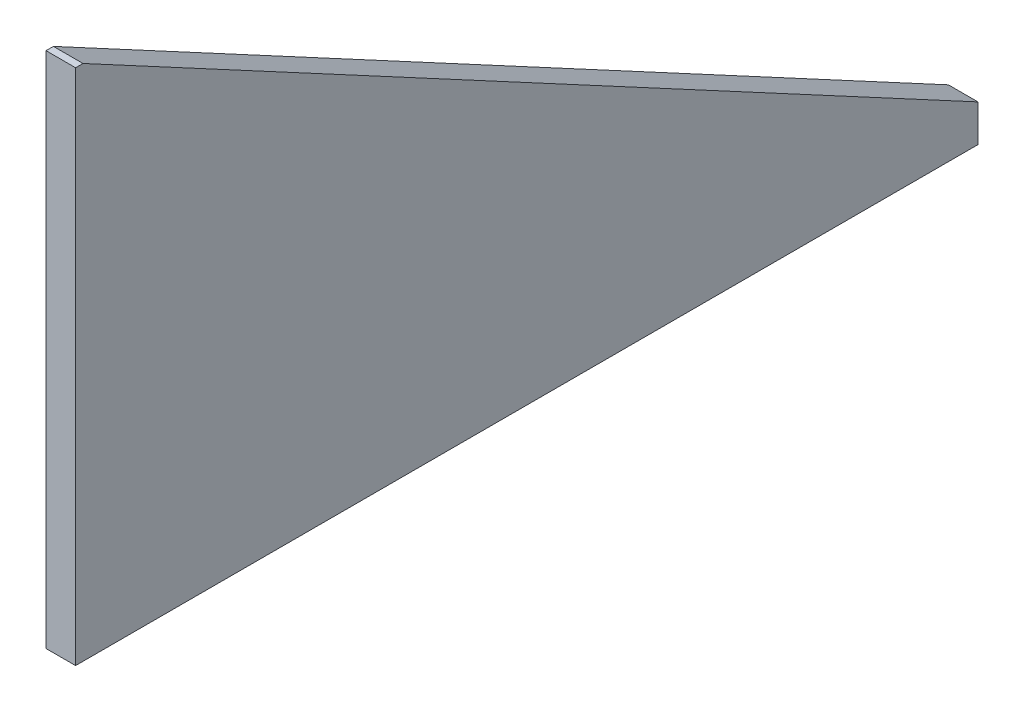
SolidWorks part; units mm, degrees
material "普通碳钢"
ref_plane "前视基准面" through (0, 0, 0) normal (0, 0, 1) x (1, 0, 0)
ref_plane "上视基准面" through (0, 0, 0) normal (0, 1, 0) x (1, 0, 0)
ref_plane "右视基准面" through (0, 0, 0) normal (1, 0, 0) x (0, 0, -1)
sketch "草图1" plane through (0, 0, 0) normal (1, 0, 0) x (0, 0, -1)
  line L0 (0, 0) -> (0, 280)
  line L1 (0, 280) -> (4, 280)
  line L2 (4, 280) -> (488, 20)
  line L3 (488, 20) -> (488, 0)
  line L4 (488, 0) -> (0, 0)
  dimension "D1" = 488
  dimension "D2" = 4
  dimension "D3" = 280
  dimension "D4" = 20
base flange "基体-法兰1" sketch "草图1" thickness 16 reverse thickness direction no parameters "D1"=10
sketch "草图6" plane through (0, 0, 0) normal (1, 0, 0) x (0, 0, -1)
  line L0 (4, 280) -> (0, 280) construction
  line L1 (0, 280) -> (488, 280)
  line L2 (0, 280) -> (0, 0)
  line L3 (0, 0) -> (488, 0)
  line L4 (488, 280) -> (488, 0)
  line L5 (0, 280) -> (0, 0) construction
  line L6 (0, 0) -> (488, 0) construction
  line L7 (488, 0) -> (488, 20) construction
  dimension "D1" = 488
  dimension "D2" = 280
sketch "折弯-线1" plane through (0, 0, 0) normal (0, 1, 0) x (1, 0, 0)
sketch "边界框1" plane through (0, 0, 0) normal (0, 1, 0) x (1, 0, 0)
sheet metal parameters "钣金1" thickness 16 parameters "D1"=10
flat pattern "平板型式1" [suppressed]
sketch "折弯-线2" plane through (0, 0, 0) normal (0, 1, 0) x (1, 0, 0)
sketch "边界框2" [suppressed] plane through (0, 0, 0) normal (0, 1, 0) x (1, 0, 0)
